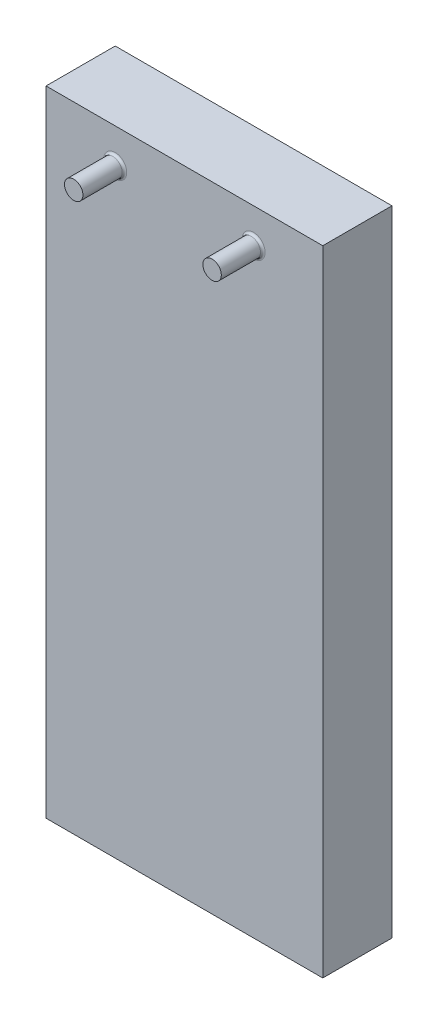
SolidWorks part; units mm, degrees
ref_plane "Front Plane" through (0, 0, 0) normal (0, 0, 1) x (1, 0, 0)
ref_plane "Top Plane" through (0, 0, 0) normal (0, 1, 0) x (1, 0, 0)
ref_plane "Right Plane" through (0, 0, 0) normal (1, 0, 0) x (0, 0, -1)
sketch "Sketch1" plane through (0, 0, 0) normal (0, 1, 0) x (1, 0, 0)
  line L1 (-60, -15) -> (60, -15)
  line L2 (-60, -15) -> (-60, 15)
  line L3 (-60, 15) -> (60, 15)
  line L4 (60, -15) -> (60, 15)
  line L5 (-60, -15) -> (60, 15) construction
  line L6 (-60, 15) -> (60, -15) construction
  point P0 (0, 0)
  dimension "D1" = 120
  dimension "D2" = 30
extrude "Boss-Extrude1" add sketch "Sketch1" along normal blind 275
sketch "Sketch2" plane through (0, 0, 15) normal (0, 0, 1) x (1, 0, 0)
  line L0 (-60, 245) -> (60, 245)
  line L1 (-60, 275) -> (-60, 0) construction
  line L2 (60, 275) -> (60, 0) construction
  line L3 (-60, 275) -> (60, 275) construction
  line L4 (-60, 245) -> (-60, 275)
  line L5 (-60, 260) -> (60, 260) construction
  circle A2 centre (-30, 260) radius 4
  circle A3 centre (30, 260) radius 4
  dimension "D4" = 8
  dimension "D1" = 30
  dimension "D2" = 30
  dimension "D3" = 30
extrude "Boss-Extrude2" add sketch "Sketch2" along normal blind 18 contours L5 A3 | A3 L5 | L5 A2 | A2 L5 region at (-30, 261.6977, 15) region at (30, 261.6977, 15) region at (30, 258.3023, 15) region at (-30, 258.3023, 15)
fillet "Fillet1" radius 1 2 edges at (26, 260, 15) (-34, 260, 15)
equation "\"PCWidth\"= 242mm'Distance of longest part parallel to GPU(ussually GPU)"
equation "\"PCLength\"= 320mm'Length across I/O from PS to GPU"
equation "\"PCHeight\"= 172mm'Tallest point with mobo laying flat"
equation "\"WallThickness\"= 9mm'Thickness of each outer tank wall"
equation "\"ThermoBarrierThickness\"= 3mm'Thickness of barrier between hot side and cold side"
equation "\"HotSideGap\"= 25mm'Space in the hot side for a pump"
equation "\"PCClearance\"= 30mm'Clearance from top of tank to top of PC"
equation "\"RadiatorHeight\"= 275mm'Final Height from ground of radiators"
equation "\"D1@Boss-Extrude1\"=\"RadiatorHeight\""
